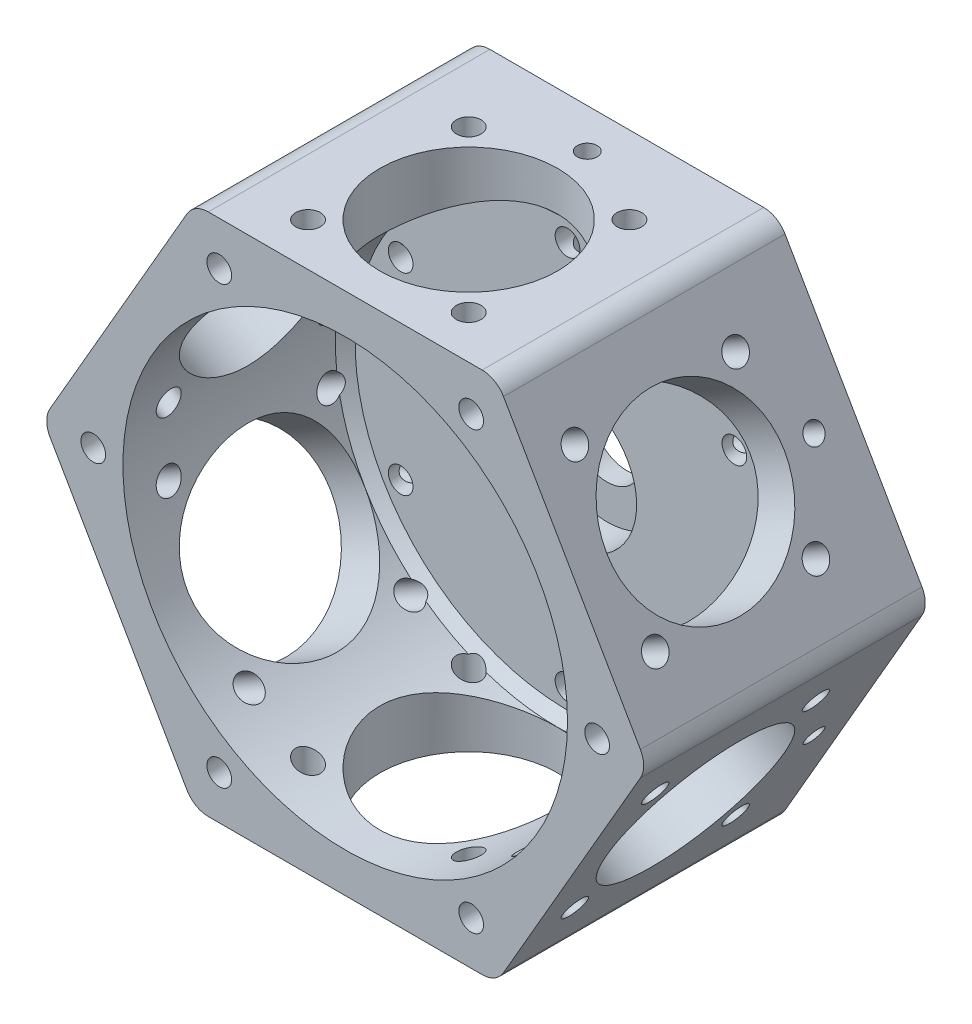
SolidWorks part; units mm, degrees
ref_plane "Front Plane" through (0, 0, 0) normal (0, 0, 1) x (1, 0, 0)
ref_plane "Top Plane" through (0, 0, 0) normal (0, 1, 0) x (1, 0, 0)
ref_plane "Right Plane" through (0, 0, 0) normal (1, 0, 0) x (0, 0, -1)
sketch "Sketch1" plane through (0, 0, 0) normal (0, 0, 1) x (1, 0, 0)
  line L1 (-59.7558, -2.5) -> (-32.0429, -50.5)
  line L2 (-27.7128, -53) -> (27.7128, -53)
  line L3 (32.0429, -50.5) -> (59.7558, -2.5)
  line L4 (59.7558, 2.5) -> (32.0429, 50.5)
  line L5 (27.7128, 53) -> (-27.7128, 53)
  line L6 (-32.0429, 50.5) -> (-59.7558, 2.5)
  circle A0 centre (0, 0) radius 53 construction
  arc A1 (-59.7558, -2.5) -> (-59.7558, 2.5) centre (-55.4256, 0) cw
  arc A2 (-32.0429, -50.5) -> (-27.7128, -53) centre (-27.7128, -48) ccw
  arc A3 (27.7128, -53) -> (32.0429, -50.5) centre (27.7128, -48) ccw
  arc A4 (59.7558, -2.5) -> (59.7558, 2.5) centre (55.4256, 0) ccw
  arc A5 (32.0429, 50.5) -> (27.7128, 53) centre (27.7128, 48) ccw
  arc A6 (-27.7128, 53) -> (-32.0429, 50.5) centre (-27.7128, 48) ccw
  dimension "D2" = 5
  dimension "D1" = 106
extrude "Boss-Extrude1" add sketch "Sketch1" along normal blind 25 and the other way blind 32
sketch "Sketch2" plane through (0, 0, 25) normal (0, 0, 1) x (1, 0, 0)
  circle A0 centre (0, 0) radius 45
  dimension "D1" = 90
extrude "Cut-Extrude1" cut sketch "Sketch2" against normal blind 45
sketch "Sketch3" plane through (-45.8993, 26.5, 0) normal (-0.866, 0.5, 0) x (0, 0, 1)
  circle A0 centre (0, 0) radius 18
  dimension "D1" = 36
extrude "Cut-Extrude2" cut sketch "Sketch3" against normal up to surface (11.7568 mm away) up to face at (45, 0, -20)
pattern_circular "CirPattern1" count 6 over 360 about axis through (0, 0, -20) along (0, 0, 1) of "Cut-Extrude2"
sketch "Sketch4" plane through (0, 0, 25) normal (0, 0, 1) x (1, 0, 0)
  line L0 (0, 0) -> (-30.2128, 52.3301) construction
  circle A0 centre (0, 0) radius 51
  arc A1 (-27.7128, 53) -> (-32.0429, 50.5) centre (-27.7128, 48) ccw construction
  dimension "D1" = 102
hole_wizard "M6 Tapped Hole1" positions "Sketch5" profile "Sketch6" tap size "M6" standard "ISO"
sketch "Sketch5" plane through (0, 0, 25) normal (0, 0, 1) x (1, 0, 0)
  line L0 (0, 0) -> (-30.2128, 52.3301) construction
  circle A0 centre (0, 0) radius 51 construction
  point P0 (-25.5, 44.1673)
sketch "Sketch6" plane through (-25.5, 44.1673, 25) normal (1, 0, 0) x (0, -1, 0)
  line L0 (0, 0) -> (0, 13.5022)
  line L1 (0, 13.5022) -> (2.5, 12)
  line L2 (2.5, 12) -> (2.5, 0)
  line L5 (2.5, 0) -> (0, 0)
  line L10 (0, 13.5022) -> (-2.5, 12) construction
  line L11 (0, -6.35) -> (0, 107.95) construction
  dimension "Tap Drill Dia." = 5
  dimension "Tap Drill Depth" = 12
  dimension "Drill Angle" = 118
cosmetic thread "Hole Thread2" parameters "D1"=12, "D2"=6
pattern_circular "CirPattern2" count 6 over 360 about axis through (0, 0, 25) along (0, 0, 1) of "M6 Tapped Hole1"
sketch "Sketch7" plane through (-45.8993, 26.5, 0) normal (-0.866, 0.5, 0) x (0, 0, 1)
  line L2 (0, 0) -> (-23, 0) construction
  line L3 (0, 0) -> (-16.2635, 16.2635) construction
  circle A0 centre (0, 0) radius 23 construction
  dimension "D1" = 46
  dimension "D2" = 45
hole_wizard "M6 Tapped Hole3" positions "Sketch10" profile "Sketch11" tap size "M6" standard "ISO"
sketch "Sketch10" plane through (-45.8993, 26.5, 0) normal (-0.866, 0.5, 0) x (0, 0, 1)
  point P0 (-16.2635, 16.2635)
sketch "Sketch11" plane through (-37.7676, 40.5846, -16.2635) normal (0, 0, 1) x (-0.5, -0.866, 0)
  line L0 (0, 0) -> (0, 16.5022)
  line L1 (0, 16.5022) -> (2.5, 15)
  line L2 (2.5, 15) -> (2.5, 0)
  line L5 (2.5, 0) -> (0, 0)
  line L10 (0, 16.5022) -> (-2.5, 15) construction
  line L11 (0, -6.35) -> (0, 107.95) construction
  dimension "Tap Drill Dia." = 5
  dimension "Tap Drill Depth" = 15
  dimension "Drill Angle" = 118
cosmetic thread "Hole Thread1" parameters "D1"=12, "D2"=6
pattern_circular "CirPattern4" count 4 over 360 about axis through (-45.8993, 26.5, 0) along (-0.866, 0.5, 0) of "M6 Tapped Hole3"
pattern_circular "CirPattern6" count 6 over 360 about axis through (0, 0, -20) along (0, 0, 1) of "M6 Tapped Hole3", "CirPattern4"
sketch "Sketch12" plane through (0, 53, 0) normal (0, 1, 0) x (1, 0, 0)
  circle A0 centre (0, 24) radius 2
  dimension "D1" = 4
  dimension "D2" = 24
extrude "Cut-Extrude3" cut sketch "Sketch12" against normal blind 36
pattern_circular "CirPattern7" count 6 over 360 about axis through (0, 0, -20) along (0, 0, 1) of "Cut-Extrude3"
sketch "Sketch13" plane through (0, 0, -32) normal (0, 0, -1) x (-1, 0, 0)
  circle A0 centre (0, 0) radius 7
  dimension "D1" = 14
extrude "Cut-Extrude4" cut sketch "Sketch13" against normal up to surface (12 mm away) up to face at (45, 0, -20)
sketch "Sketch14" plane through (0, 0, -20) normal (0, 0, 1) x (1, 0, 0)
  circle A0 centre (0, 0) radius 14
  dimension "D1" = 28
extrude "Cut-Extrude5" cut sketch "Sketch14" against normal blind 8
sketch "Sketch15" plane through (0, 0, -32) normal (0, 0, -1) x (-1, 0, 0)
  circle A0 centre (0, 0) radius 20 construction
  circle A1 centre (0, 20) radius 2
  dimension "D1" = 40
  dimension "D2" = 4
extrude "Cut-Extrude6" cut sketch "Sketch15" against normal blind 8
pattern_circular "CirPattern8" count 6 over 360 about axis through (0, 0, -32) along (0, 0, -1) of "Cut-Extrude6"
chamfer "Chamfer1" distance 2 angle 45 1 edges at (45, 0, -20)
sketch "Sketch16" plane through (0, 0, -32) normal (0, 0, -1) x (-1, 0, 0)
  circle A2 centre (0, 0) radius 39 construction
  dimension "D1" = 78
hole_wizard "M6 Tapped Hole4" positions "Sketch17" profile "Sketch18" tap size "M6" standard "ISO"
sketch "Sketch17" plane through (0, 0, -32) normal (0, 0, -1) x (-1, 0, 0)
  circle A0 centre (0, 0) radius 39 construction
  point P0 (0, 39)
sketch "Sketch18" plane through (0, 39, -32) normal (1, 0, 0) x (0, 1, 0)
  line L0 (0, 0) -> (0, 16.5022)
  line L1 (0, 16.5022) -> (2.5, 15)
  line L2 (2.5, 15) -> (2.5, 0)
  line L5 (2.5, 0) -> (0, 0)
  line L10 (0, 16.5022) -> (-2.5, 15) construction
  line L11 (0, -6.35) -> (0, 107.95) construction
  dimension "Tap Drill Dia." = 5
  dimension "Tap Drill Depth" = 15
  dimension "Drill Angle" = 118
cosmetic thread "Hole Thread3" parameters "D1"=12, "D2"=6
pattern_circular "CirPattern9" count 6 over 360 about axis through (0, 0, -20) along (0, 0, 1) of "M6 Tapped Hole4"
